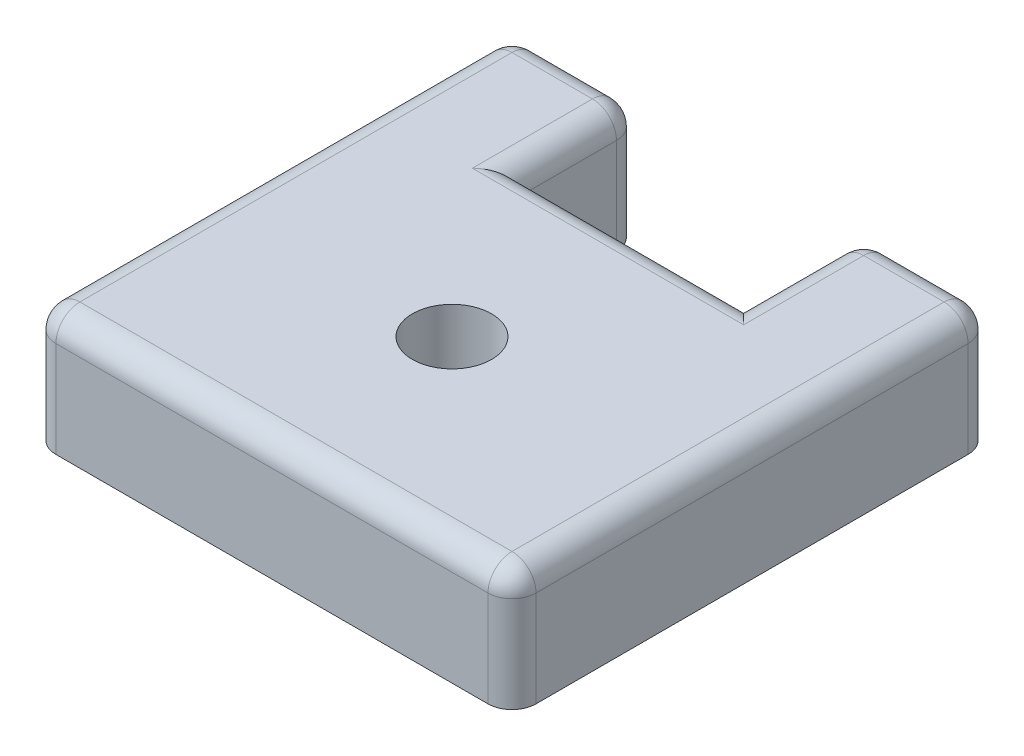
SolidWorks part; units mm, degrees
ref_plane "Front Plane" through (0, 0, 0) normal (0, 0, 1) x (1, 0, 0)
ref_plane "Top Plane" through (0, 0, 0) normal (0, 1, 0) x (1, 0, 0)
ref_plane "Right Plane" through (0, 0, 0) normal (1, 0, 0) x (0, 0, -1)
sketch "Sketch2" plane through (0, 0, 0) normal (0, 1, 0) x (1, 0, 0)
  line L0 (14.65, 20) -> (20, 20)
  line L1 (0, 0) -> (20, 0)
  line L2 (0, 0) -> (0, 20)
  line L3 (0, 20) -> (5.35, 20)
  line L4 (20, 0) -> (20, 20)
  line L6 (5.35, 20) -> (5.35, 15)
  line L7 (5.35, 15) -> (14.65, 15)
  line L8 (14.65, 20) -> (14.65, 15)
  dimension "D1" = 20
  dimension "D2" = 9.3
  dimension "D3" = 20
  dimension "D4" = 5
  dimension "D5" = 5.35
extrude "Boss-Extrude1" add sketch "Sketch2" along normal blind 5 contours L4 L0 L8 L7 L6 L3 L2 L1
fillet "Fillet1" radius 1 14 edges at (0, 5, -10) (2.675, 5, -20) (5.35, 5, -17.5) (10, 5, -15) (14.65, 5, -17.5) (17.325, 5, -20) (20, 5, -10) (10, 5, 0) (0, 2.5, 0) (20, 2.5, 0) (20, 2.5, -20) (0, 2.5, -20) (14.65, 2.5, -20) (5.35, 2.5, -20)
sketch "Sketch3" plane through (0, 5, 0) normal (0, 1, 0) x (1, 0, 0)
  line L0 (10, 1) -> (10, 14) construction
  line L1 (1, 1) -> (19, 1) construction
  line L2 (15.65, 14) -> (4.35, 14) construction
  circle A0 centre (10, 7.5) radius 1.65
  dimension "D1" = 3.3
extrude "Cut-Extrude1" cut sketch "Sketch3" against normal through all
